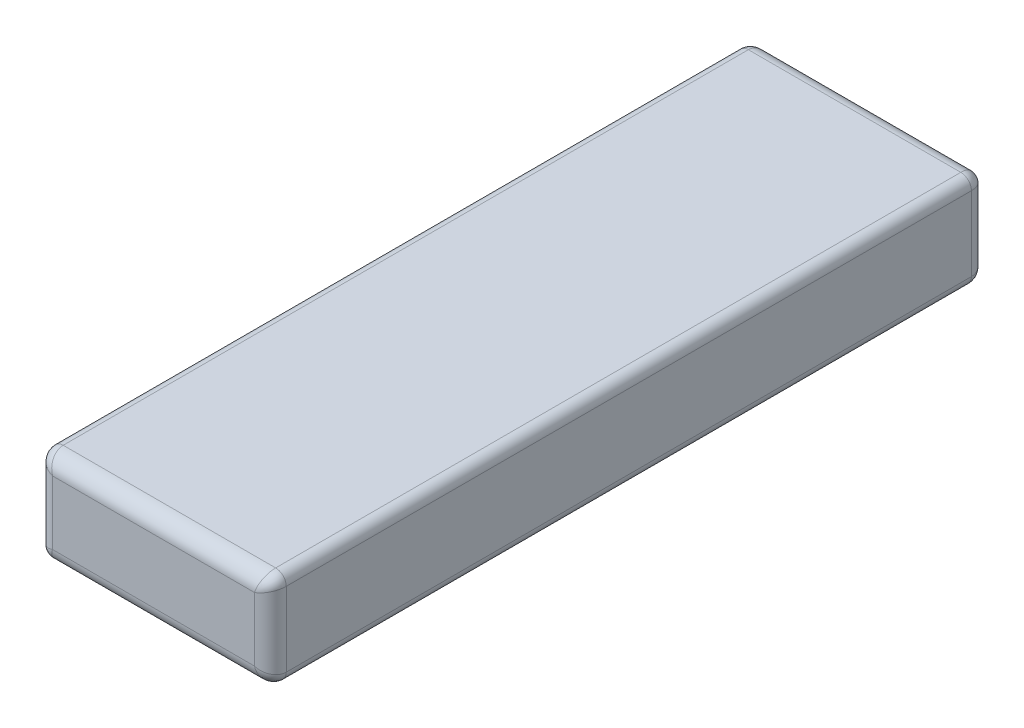
SolidWorks part; units mm, degrees
ref_plane "Front Plane" through (0, 0, 0) normal (0, 0, 1) x (1, 0, 0)
ref_plane "Top Plane" through (0, 0, 0) normal (0, 1, 0) x (1, 0, 0)
ref_plane "Right Plane" through (0, 0, 0) normal (1, 0, 0) x (0, 0, -1)
sketch "Sketch1" plane through (0, 0, 0) normal (0, 0, 1) x (1, 0, 0)
  line L1 (-22, 9) -> (22, 9)
  line L2 (-22, 9) -> (-22, -9)
  line L3 (-22, -9) -> (22, -9)
  line L4 (22, 9) -> (22, -9)
  line L5 (-22, 9) -> (22, -9) construction
  line L6 (-22, -9) -> (22, 9) construction
  point P0 (0, 0)
  dimension "D1" = 18
  dimension "D2" = 44
extrude "Boss-Extrude1" add sketch "Sketch1" along normal blind 135
fillet "Fillet1" radius 2 4 edges at (-22, -9, 67.5) (22, -9, 67.5) (-22, 9, 67.5) (22, 9, 67.5)
fillet "Fillet2" radius 3 16 edges at (21.4142, 8.4142, 0) (22, 0, 0) (21.4142, -8.4142, 0) (0, -9, 0) (-21.4142, -8.4142, 0) (-22, 0, 0) (-21.4142, 8.4142, 0) (21.4142, 8.4142, 135) (22, 0, 135) (21.4142, -8.4142, 135) (0, -9, 135) (-21.4142, -8.4142, 135) (-22, 0, 135) (-21.4142, 8.4142, 135) (0, 9, 0) (0, 9, 135)
